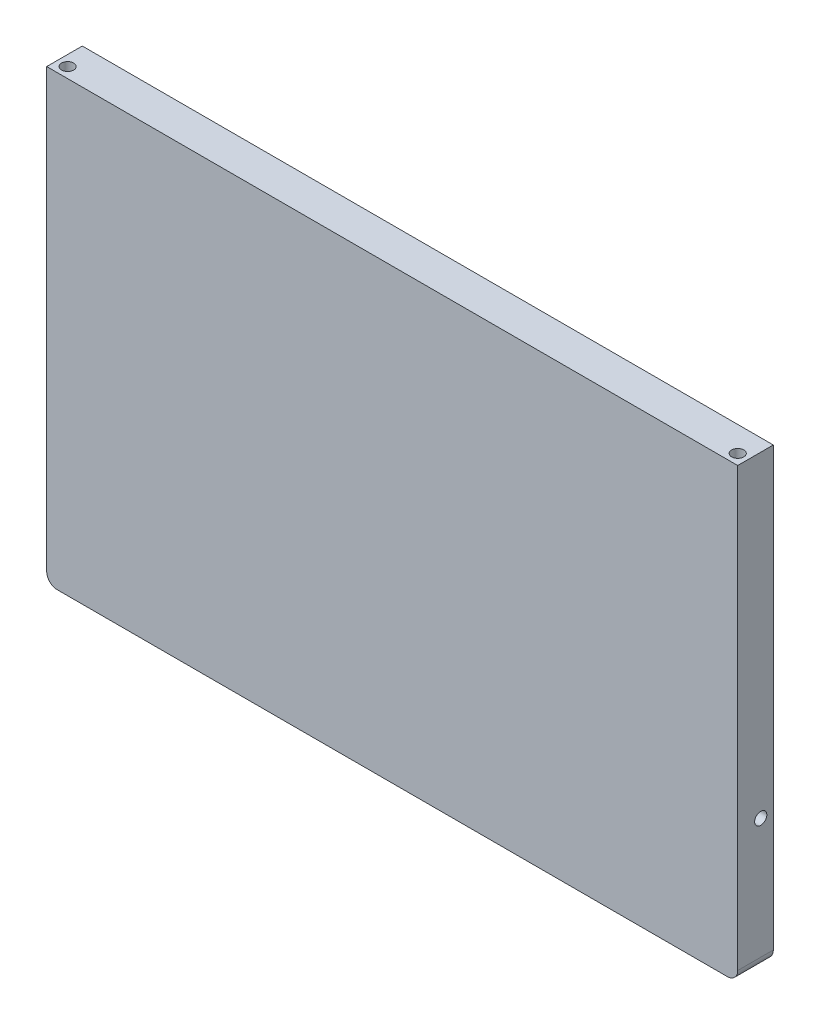
SolidWorks part; units mm, degrees
material "PLA"
ref_plane "Front Plane" through (0, 0, 0) normal (0, 0, 1) x (1, 0, 0)
ref_plane "Top Plane" through (0, 0, 0) normal (0, 1, 0) x (1, 0, 0)
ref_plane "Right Plane" through (0, 0, 0) normal (1, 0, 0) x (0, 0, -1)
sketch "Sketch1" plane through (0, 0, 0) normal (0, 0, 1) x (1, 0, 0)
  line L0 (0, 0) -> (0, -138.8145) construction
  line L1 (-82.55, -80.8019) -> (82.55, -80.8019)
  line L2 (-82.55, -80.8019) -> (-82.55, 9.1981)
  line L3 (-82.55, 9.1981) -> (82.55, 9.1981)
  line L4 (82.55, -80.8019) -> (82.55, 9.1981)
  point P7 (0, -80.8019)
  dimension "D1" = 165.1
  dimension "D2" = 90
extrude "Boss-Extrude1" add sketch "Sketch1" along normal blind 5
sketch "Sketch2" plane through (0, 9.1981, 0) normal (0, 1, 0) x (1, 0, 0)
  line L0 (-82.55, -5) -> (-82.55, 0) construction
  line L1 (82.55, -5) -> (82.55, 0) construction
  circle A0 centre (-80.05, -2.5) radius 1.45
  circle A1 centre (80.05, -2.5) radius 1.45
  point P7 (-82.55, -2.5)
  dimension "D2" = 2.9
  dimension "D4" = 2.9
  dimension "D1" = 2.5
  dimension "D3" = 2.5
extrude "Cut-Extrude1" cut sketch "Sketch2" against normal blind 7 contours A1 | A0
sketch "Sketch4" plane through (0, 0, 0) normal (0, 0, -1) x (-1, 0, 0)
  line L4 (-82.55, 9.1981) -> (-82.55, -80.8019)
  line L5 (-82.55, -80.8019) -> (82.55, -80.8019)
  line L6 (82.55, -80.8019) -> (82.55, 9.1981)
  line L7 (82.55, 9.1981) -> (-82.55, 9.1981)
  line L8 (-82.55, 9.1981) -> (-82.55, -80.8019)
  line L9 (-82.55, -80.8019) -> (82.55, -80.8019)
  line L10 (82.55, -80.8019) -> (82.55, 9.1981)
  line L11 (82.55, 9.1981) -> (-82.55, 9.1981)
  dimension "D1" = 0
extrude "Boss-Extrude2" add sketch "Sketch4" along normal blind 3.5
ref_plane "Plane1" through (-27.79, 0, 0) normal (-1, 0, 0) x (0, 0, 1)
sketch "Sketch8" plane through (82.55, 0, 0) normal (1, 0, 0) x (0, 0, -1)
  line L2 (0.5, -68.0019) -> (0.5, -65.1019) construction
  circle A2 centre (0.5, -66.5519) radius 1.45
extrude "Cut-Extrude5" cut sketch "Sketch8" against normal blind 3
mirror "Mirror2" about plane through (0, 0, 0) normal (1, 0, 0) of "Cut-Extrude5"
sketch "Sketch10" plane through (0, -80.8019, 0) normal (0, -1, 0) x (1, 0, 0)
  line L4 (-82.55, 5) -> (-82.55, -3.5)
  line L5 (-82.55, -3.5) -> (82.55, -3.5)
  line L6 (82.55, -3.5) -> (82.55, 5)
  line L7 (82.55, 5) -> (-82.55, 5)
  line L8 (-82.55, 5) -> (-82.55, -3.5)
  line L9 (-82.55, -3.5) -> (82.55, -3.5)
  line L10 (82.55, -3.5) -> (82.55, 5)
  line L11 (82.55, 5) -> (-82.55, 5)
  dimension "D1" = 0
extrude "Boss-Extrude4" add sketch "Sketch10" along normal blind 17
fillet "Fillet1" radius 2.5 2 edges at (82.55, -97.8019, 0.75) (-82.55, -97.8019, 0.75)
sketch "Sketch11" plane through (0, 0, -3.5) normal (0, 0, -1) x (-1, 0, 0)
  line L0 (0, 9.1981) -> (0, -97.8019) construction
  line L1 (82.55, 9.1981) -> (-82.55, 9.1981) construction
  line L2 (80.05, -97.8019) -> (-80.05, -97.8019) construction
  line L3 (-82.55, -43.0519) -> (82.55, -43.0519) construction
  line L4 (-82.55, 9.1981) -> (-82.55, -95.3019) construction
  line L5 (82.55, -95.3019) -> (82.55, 9.1981) construction
  line L7 (-51.7, 2.3981) -> (51.7, 2.3981)
  line L8 (-51.7, 2.3981) -> (-51.7, -88.5019)
  line L9 (-51.7, -88.5019) -> (51.7, -88.5019)
  line L10 (51.7, 2.3981) -> (51.7, -88.5019)
  point P16 (0, 2.3981)
  point P17 (-51.7, -43.0519)
  dimension "D1" = 103.4
  dimension "D2" = 90.9
extrude "Cut-Extrude6" cut sketch "Sketch11" against normal blind 6
